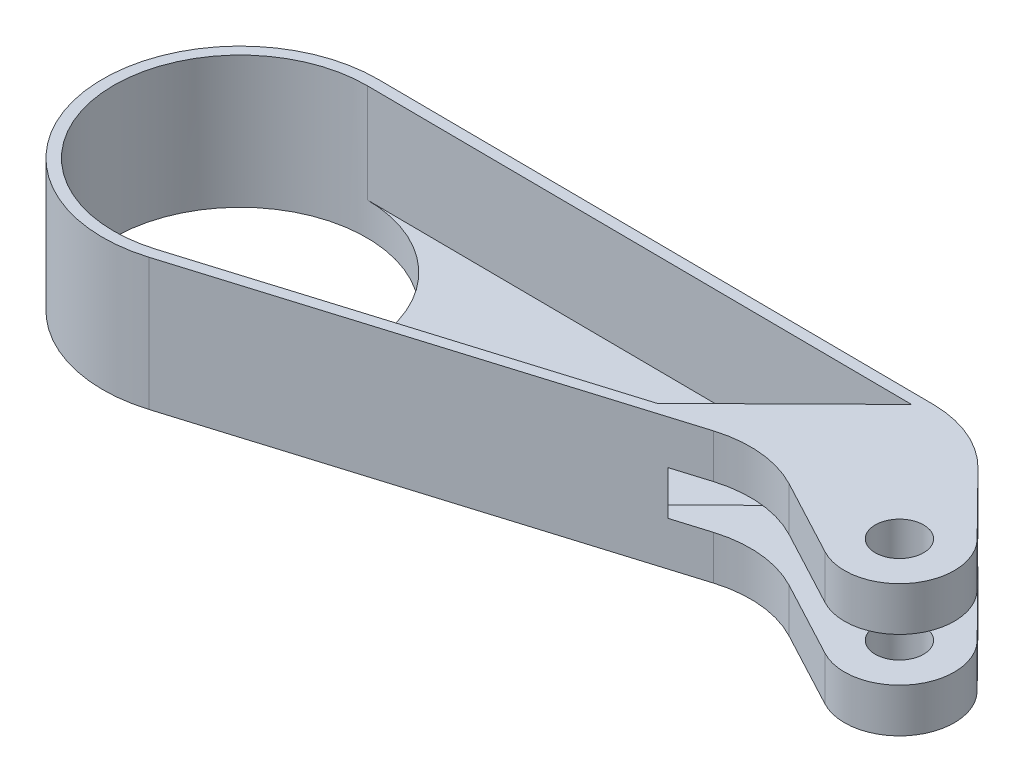
SolidWorks part; units mm, degrees
ref_plane "Front Plane" through (0, 0, 0) normal (0, 0, 1) x (1, 0, 0)
ref_plane "Top Plane" through (0, 0, 0) normal (0, 1, 0) x (1, 0, 0)
ref_plane "Right Plane" through (0, 0, 0) normal (1, 0, 0) x (0, 0, -1)
sketch "Sketch1" plane through (0, 0, 0) normal (0, 1, 0) x (1, 0, 0)
  line L0 (0, 0) -> (300, 0) construction
  line L1 (0, 0) -> (0, 62.5) construction
  line L2 (0.4468, 62.4984) -> (18.2292, -59.7825) construction
  line L3 (317.8036, 17.5508) -> (288.2469, -22.065) construction
  line L4 (300, 0) -> (300, 25) construction
  line L5 (0.4468, 62.4984) -> (409.655, 59.573)
  line L6 (409.655, 59.573) -> (18.2292, -59.7825)
  line L7 (288.2469, -22.065) -> (234.9772, 6.3094)
  line L8 (317.8036, 17.5508) -> (275.4321, 60.5325)
  line L9 (275.4321, 60.5325) -> (234.9772, 6.3094) construction
  circle A0 centre (0, 0) radius 62.5
  circle A1 centre (300, 0) radius 11
  circle A2 centre (300, 0) radius 25
  circle A3 centre (0, 0) radius 57.5
  point P11 (307.1813, 28.3262)
  dimension "D2" = 125
  dimension "D3" = 22
  dimension "D4" = 50
  dimension "D7" = 115
  dimension "D1" = 300
  dimension "D5" = 135
  dimension "D6" = 135
extrude "Boss-Extrude2" add sketch "Sketch1" along normal blind 30 and the other way blind 30 contours A0 A3 | A2 L8 L6 | A2 L6 L7 | A0 L6 L8 L5 | A2 A1 region at (151.1228, 0, -21.8113) region at (43.0974, 0, -42.7904) region at (306.3702, 0, -25.1268) region at (263.8681, 0, -3.506) region at (305.9699, 0, -23.5479)
fillet "Fillet1" radius 50 2 edges at (234.9772, 0, -6.3094) (275.4321, 0, -60.5325)
sketch "Sketch4" plane through (169.9482, 0, -167.5355) normal (0.7121, 0, -0.702) x (-0.702, 0, -0.7121)
  line L0 (-296.311, 0) -> (0, 0) construction
  line L1 (-179.7518, 87.9908) -> (-179.7518, -107.4173) construction
  line L2 (-135.6797, 10) -> (-135.6797, -10)
  line L3 (-135.6797, 10) -> (-276.1794, 10)
  line L4 (-135.6797, -10) -> (-276.1794, -10)
  line L5 (-276.1794, 10) -> (-276.1794, -10)
  dimension "D1" = 20
  dimension "D2" = 10
extrude "Cut-Extrude1" cut sketch "Sketch4" against normal blind 100
sketch "Sketch5" plane through (0, 30, 0) normal (0, 1, 0) x (1, 0, 0)
  line L0 (16.7708, -54.9999) -> (191.5306, -1.7113)
  line L1 (249.7847, 55.7157) -> (191.5306, -1.7113)
  line L2 (215.1671, 0.2687) -> (18.2292, -59.7825) construction
  line L3 (0.4111, 57.4985) -> (249.7847, 55.7157)
  line L4 (193.9855, 0.7087) -> (254.8202, 60.6798) construction
  line L5 (0.4468, 62.4984) -> (254.722, 60.6806) construction
  arc A0 (0.4111, 57.4985) -> (0, -57.5) centre (0, 0) cw
  circle A1 centre (0, 0) radius 57.5 construction
  circle M11 centre (0, 0) radius 57.5
  dimension "D1" = 5
  dimension "D2" = 5
extrude "Cut-Extrude2" cut sketch "Sketch5" against normal blind 45 contours L3 L0 M11 region at (124.6301, 30, -19.0626)
